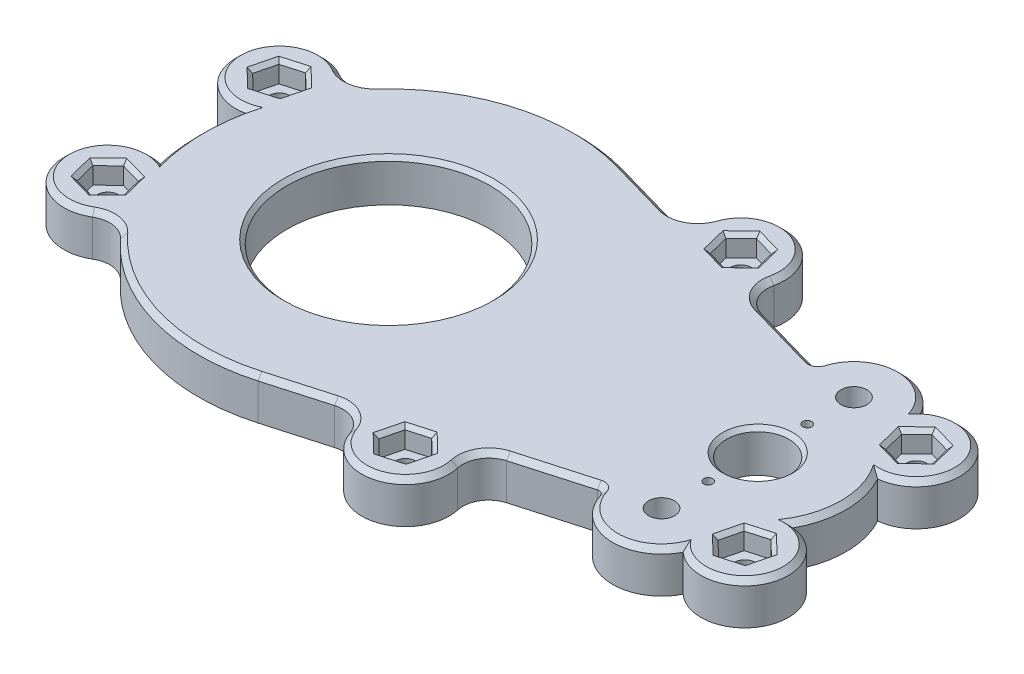
SolidWorks part; units mm, degrees
ref_plane "Front Plane" through (0, 0, 0) normal (0, 0, 1) x (1, 0, 0)
ref_plane "Top Plane" through (0, 0, 0) normal (0, 1, 0) x (1, 0, 0)
ref_plane "Right Plane" through (0, 0, 0) normal (1, 0, 0) x (0, 0, -1)
sketch "Sketch1" plane through (0, 0, 0) normal (0, 1, 0) x (1, 0, 0)
  line L0 (0, 73.0538) -> (0, -65.1274) construction
  line L1 (35.5, 6.365) -> (-28.5632, 24.502) construction
  line L2 (-70.6215, 0) -> (67.3742, 0) construction
  line L3 (35.5, -6.365) -> (-28.5632, -24.502) construction
  line L4 (4.5177, -15.1364) -> (0.1592, 0.2585)
  line L5 (0.1592, 0.2585) -> (4.6815, 1.5388)
  line L6 (4.6815, 1.5388) -> (9.04, -13.8561)
  line L7 (9.04, -13.8561) -> (9.5848, -15.7805)
  line L8 (9.5848, -15.7805) -> (5.0625, -17.0608)
  line L9 (5.0625, -17.0608) -> (4.5177, -15.1364)
  line L10 (-35.5, 0) -> (-60.5, 0) construction
  line L11 (-35.5, 0) -> (-35.5, 25) construction
  line L13 (-100, -75) -> (100, -75)
  line L14 (-100, -75) -> (-100, 75)
  line L15 (-100, 75) -> (100, 75)
  line L16 (100, -75) -> (100, 75)
  line L17 (-100, -75) -> (100, 75) construction
  line L18 (-100, 75) -> (100, -75) construction
  circle A0 centre (35.5, 0) radius 6
  circle A1 centre (-35.5, 0) radius 13.5
  circle A2 centre (-35.5, 0) radius 25.465 construction
  circle A3 centre (35.5, 0) radius 6.365 construction
  circle A4 centre (-60.5, 0) radius 2
  circle A5 centre (-35.5, 25) radius 2
  circle A6 centre (-10.5, 0) radius 2
  circle A7 centre (-35.5, -25) radius 2
  circle A8 centre (35.5, 18.5) radius 2.5
  circle A9 centre (35.5, -18.5) radius 2.5
  point P35 (0, 0)
  dimension "D1" = 12
  dimension "D2" = 27
  dimension "D5" = 50.93
  dimension "D6" = 12.73
  dimension "D12" = 4
  dimension "D19" = 5
  dimension "D3" = 71
  dimension "D4" = 35.5
  dimension "D7" = 90
  dimension "D8" = 27.5
  dimension "D9" = 4.7
  dimension "D10" = 16
  dimension "D11" = 2
  dimension "D13" = 25
  dimension "D15" = 90
  dimension "D16" = 25
  dimension "D17" = 200
  dimension "D18" = 150
  dimension "D20" = 18.5
  dimension "D14" = 4
extrude "Boss-Extrude1" add sketch "Sketch1" along normal blind 4
sketch "Sketch3" plane through (0, 4, 0) normal (0, 1, 0) x (1, 0, 0)
  line L0 (-26.5739, 31.2502) -> (39.0704, 12.5001)
  line L1 (-100, -75) -> (100, -75)
  line L2 (-100, -75) -> (-100, 75)
  line L3 (-100, 75) -> (100, 75)
  line L4 (100, -75) -> (100, 75)
  line L5 (-35.5, 0) -> (35.5, 0) construction
  line L6 (-26.5739, -31.2502) -> (39.0704, -12.5001)
  arc A0 (-26.5739, 31.2502) -> (-26.5739, -31.2502) centre (-35.5, 0) ccw
  arc A1 (39.0704, -12.5001) -> (39.0704, 12.5001) centre (35.5, 0) ccw
  dimension "D1" = 65
  dimension "D2" = 26
extrude "Boss-Extrude2" add sketch "Sketch3" along normal blind 8.25
sketch "Sketch6" plane through (0, 12.25, 0) normal (0, 1, 0) x (1, 0, 0)
  circle A0 centre (35.5, 18.5) radius 5.4
  circle A1 centre (35.5, -18.5) radius 5.4
  dimension "D1" = 10.8
extrude "Cut-Extrude2" cut sketch "Sketch6" against normal up to surface (8.25 mm away) up to face at (-35.5, 4, 27)
fillet "Fillet1" radius 2.5 4 edges at (9.5848, 2, 15.7805) (5.0625, 2, 17.0608) (4.6815, 2, -1.5388) (0.1592, 2, -0.2585)
fillet "Fillet2" radius 5 4 edges at (36.5847, 8.125, 13.2101) (31.7849, 8.125, 14.5811) (36.5847, 8.125, -13.2101) (31.7849, 8.125, -14.5811)
sketch "Sketch2" plane through (0, 4, 0) normal (0, 1, 0) x (1, 0, 0)
  line L0 (29.5, 0) -> (41.5, 0) construction
  line L1 (35.5, 0) -> (35.5, -6) construction
  line L2 (35.5, 0) -> (35.5, 6) construction
  circle A0 centre (-35.5, 25) radius 4.4
  circle A1 centre (-10.5, 0) radius 4.4
  circle A2 centre (-35.5, -25) radius 4.4
  circle A3 centre (-60.5, 0) radius 4.4
  circle A4 centre (35.5, 0) radius 6 construction
  circle A7 centre (35.5, 18.5) radius 5.4
  circle A8 centre (35.5, -18.5) radius 5.4
  arc A9 (40.6003, 16.7261) -> (30.3389, 20.0883) centre (35.5, 18.5) ccw construction
  dimension "D1" = 8.8
extrude "Cut-Extrude1" cut sketch "Sketch2" against normal blind 2
sketch "Sketch8" plane through (0, 0, 0) normal (0, -1, 0) x (1, 0, 0)
  line L0 (-35.5, 0) -> (-100, 0) construction
  line L1 (-100, -75) -> (-100, 75) construction
  line L2 (-35.5, 0) -> (100, 0) construction
  line L3 (100, 75) -> (100, -75) construction
  line L4 (49.5, 21.4955) -> (49.5, -20.5045) construction
  line L5 (0, 32.8542) -> (0, -34.16) construction
  line L6 (-73, 27.0496) -> (-73, -26.9504) construction
  line L11 (-26.5739, -31.2502) -> (24.1868, -16.7513)
  line L12 (24.1868, 16.7513) -> (-26.5739, 31.2502)
  line L13 (-26.5739, -31.2502) -> (24.1868, -16.7513) construction
  line L14 (24.1868, 16.7513) -> (-26.5739, 31.2502) construction
  circle A0 centre (-35.5, 0) radius 32.5 construction
  arc A1 (-26.5739, 31.2502) -> (-26.5739, -31.2502) centre (-35.5, 0) ccw construction
  circle A13 centre (49.5, 16.5) radius 2
  circle A14 centre (-73, 16.5) radius 2
  circle A15 centre (0, 32.25) radius 2
  circle A16 centre (49.5, 16.5) radius 4.4 construction
  circle A17 centre (0, 32.25) radius 4.4 construction
  circle A18 centre (-73, 16.5) radius 4.4 construction
  circle A19 centre (35.5, 18.5) radius 5.4 construction
  arc A20 (40.6003, 16.7261) -> (30.3389, 20.0883) centre (35.5, 18.5) ccw construction
  circle A21 centre (35.5, -18.5) radius 5.4 construction
  circle A22 centre (-73, -16.5) radius 4.4 construction
  circle A23 centre (-73, -16.5) radius 2
  circle A24 centre (0, -32.25) radius 4.4 construction
  circle A25 centre (0, -32.25) radius 2
  circle A26 centre (49.5, -16.5) radius 4.4 construction
  circle A27 centre (49.5, -16.5) radius 2
  circle A28 centre (49.5, 16.5) radius 8.4 construction
  circle A29 centre (0, 32.25) radius 8.4 construction
  circle A30 centre (-73, 16.5) radius 8.4 construction
  arc A44 (30.3389, -20.0883) -> (40.6003, -16.7261) centre (35.5, -18.5) ccw
  arc A45 (42.5943, -10.8936) -> (40.6003, -16.7261) centre (45.3228, -15.0835) ccw
  arc A46 (42.5943, -10.8936) -> (42.5943, 10.8936) centre (35.5, 0) ccw
  arc A47 (40.6003, 16.7261) -> (42.5943, 10.8936) centre (45.3228, 15.0835) ccw
  arc A48 (30.3389, -20.0883) -> (24.1868, -16.7513) centre (25.5601, -21.559) ccw
  arc A49 (40.6003, 16.7261) -> (30.3389, 20.0883) centre (35.5, 18.5) ccw
  arc A50 (24.1868, 16.7513) -> (30.3389, 20.0883) centre (25.5601, 21.559) ccw
  arc A51 (-26.5739, 31.2502) -> (-26.5739, -31.2502) centre (-35.5, 0) ccw
  arc A52 (30.3389, -20.0883) -> (40.6003, -16.7261) centre (35.5, -18.5) ccw construction
  arc A53 (42.5943, -10.8936) -> (40.6003, -16.7261) centre (45.3228, -15.0835) ccw construction
  arc A54 (42.5943, -10.8936) -> (42.5943, 10.8936) centre (35.5, 0) ccw construction
  arc A55 (40.6003, 16.7261) -> (42.5943, 10.8936) centre (45.3228, 15.0835) ccw construction
  arc A56 (30.3389, -20.0883) -> (24.1868, -16.7513) centre (25.5601, -21.559) ccw construction
  arc A57 (40.6003, 16.7261) -> (30.3389, 20.0883) centre (35.5, 18.5) ccw construction
  arc A58 (24.1868, 16.7513) -> (30.3389, 20.0883) centre (25.5601, 21.559) ccw construction
  arc A59 (-26.5739, 31.2502) -> (-26.5739, -31.2502) centre (-35.5, 0) ccw construction
  dimension "D1" = 0
  dimension "D2" = 4
  dimension "D4" = 33
  dimension "D5" = 49.5
  dimension "D3" = 8.8
  dimension "D8" = 16.8
  dimension "D6" = 64.5
  dimension "D7" = 73
extrude "Cut-Extrude3" cut sketch "Sketch8" against normal through all both and the other way through all
sketch "Sketch13" plane through (0, 12.25, 0) normal (0, 1, 0) x (1, 0, 0)
  line L0 (-100, 0) -> (100, 0) construction
  line L1 (-100, 75) -> (-100, -75) construction
  line L2 (100, -75) -> (100, 75) construction
  line L5 (-8.1313, 30.1424) -> (-25.4754, 35.0964)
  line L6 (5.7914, -26.1656) -> (25.2854, -20.5975)
  line L7 (-25.4754, -35.0964) -> (25.2854, -20.5975)
  line L8 (25.2854, 20.5975) -> (-25.4754, 35.0964)
  line L9 (-25.4754, -35.0964) -> (-8.1313, -30.1424)
  line L10 (25.2854, 20.5975) -> (5.7914, 26.1656)
  arc A0 (5.7914, 26.1656) -> (-8.1313, 30.1424) centre (0, 32.25) ccw
  arc A1 (50.4188, 8.1504) -> (43.8854, 22.7479) centre (49.5, 16.5) ccw
  arc A2 (-65.6518, 20.5699) -> (-71.0361, 8.3328) centre (-73, 16.5) ccw
  arc A3 (-65.6518, -20.5699) -> (-71.0361, -8.3328) centre (-73, -16.5) cw
  arc A4 (5.7914, -26.1656) -> (-8.1313, -30.1424) centre (0, -32.25) cw
  arc A5 (50.4188, -8.1504) -> (43.8854, -22.7479) centre (49.5, -16.5) cw
  arc A14 (-71.0361, 8.3328) -> (-71.0361, -8.3328) centre (-35.5, 0) ccw
  arc A15 (-65.6518, -20.5699) -> (-25.4754, -35.0964) centre (-35.5, 0) ccw
  arc A22 (44.3783, 15.412) -> (26.5158, 21.2649) centre (35.5, 18.5) ccw
  arc A23 (44.3783, 15.412) -> (44.7771, 14.2455) centre (45.3228, 15.0835) ccw
  arc A24 (44.7771, -14.2455) -> (44.7771, 14.2455) centre (35.5, 0) ccw
  arc A25 (44.7771, -14.2455) -> (44.3783, -15.412) centre (45.3228, -15.0835) ccw
  arc A26 (26.5158, -21.2649) -> (44.3783, -15.412) centre (35.5, -18.5) ccw
  arc A27 (26.5158, -21.2649) -> (25.2854, -20.5975) centre (25.5601, -21.559) ccw
  arc A28 (-25.4754, 35.0964) -> (-25.4754, -35.0964) centre (-35.5, 0) ccw
  arc A29 (25.2854, 20.5975) -> (26.5158, 21.2649) centre (25.5601, 21.559) ccw
  arc A30 (43.8854, 22.7479) -> (26.5158, 21.2649) centre (35.5, 18.5) ccw
  arc A32 (50.4188, -8.1504) -> (50.4188, 8.1504) centre (35.5, 0) ccw
  arc A34 (26.5158, -21.2649) -> (43.8854, -22.7479) centre (35.5, -18.5) ccw
  arc A35 (26.5158, -21.2649) -> (25.2854, -20.5975) centre (25.5601, -21.559) ccw
  arc A36 (-25.4754, 35.0964) -> (-65.6518, 20.5699) centre (-35.5, 0) ccw
  arc A37 (25.2854, 20.5975) -> (26.5158, 21.2649) centre (25.5601, 21.559) ccw
  dimension "D1" = 16.8
  dimension "D2" = 4
extrude "Cut-Extrude6" cut sketch "Sketch13" against normal through all both and the other way through all flip side to cut
fillet "Fillet4" radius 5 6 edges at (-65.6518, 6.125, 20.5699) (-65.6518, 6.125, -20.5699) (-8.1313, 6.125, -30.1424) (5.7914, 6.125, -26.1656) (5.7914, 6.125, 26.1656) (-8.1313, 6.125, 30.1424)
sketch "Sketch16" plane through (0, 12.25, 0) normal (0, 1, 0) x (1, 0, 0)
  line L12 (-25.4754, -35.0964) -> (-14.035, -31.8287)
  line L13 (11.6951, -24.4793) -> (25.2854, -20.5975)
  line L14 (25.2854, 20.5975) -> (11.6951, 24.4793)
  line L15 (-14.035, 31.8287) -> (-25.4754, 35.0964)
  line L16 (-25.4754, -35.0964) -> (-14.035, -31.8287)
  line L17 (11.6951, -24.4793) -> (25.2854, -20.5975)
  line L18 (25.2854, 20.5975) -> (11.6951, 24.4793)
  line L19 (-14.035, 31.8287) -> (-25.4754, 35.0964)
  arc A60 (-71.0361, 8.3328) -> (-71.0361, -8.3328) centre (-35.5, 0) ccw
  arc A61 (-71.0361, -8.3328) -> (-68.692, -23.7112) centre (-73, -16.5) ccw
  arc A62 (-62.4376, -24.6296) -> (-68.692, -23.7112) centre (-66.1277, -28.0035) ccw
  arc A63 (-62.4376, -24.6296) -> (-25.4754, -35.0964) centre (-35.5, 0) ccw
  arc A64 (-7.9372, -34.9997) -> (-14.035, -31.8287) centre (-12.6617, -36.6364) ccw
  arc A65 (-7.9372, -34.9997) -> (8.1921, -30.3926) centre (0, -32.25) ccw
  arc A66 (11.6951, -24.4793) -> (8.1921, -30.3926) centre (13.0683, -29.2871) ccw
  arc A67 (26.5158, -21.2649) -> (25.2854, -20.5975) centre (25.5601, -21.559) ccw
  arc A68 (26.5158, -21.2649) -> (43.8854, -22.7479) centre (35.5, -18.5) ccw
  arc A69 (43.8854, -22.7479) -> (50.4188, -8.1504) centre (49.5, -16.5) ccw
  arc A70 (50.4188, -8.1504) -> (50.4188, 8.1504) centre (35.5, 0) ccw
  arc A71 (50.4188, 8.1504) -> (43.8854, 22.7479) centre (49.5, 16.5) ccw
  arc A72 (43.8854, 22.7479) -> (26.5158, 21.2649) centre (35.5, 18.5) ccw
  arc A73 (25.2854, 20.5975) -> (26.5158, 21.2649) centre (25.5601, 21.559) ccw
  arc A74 (8.1921, 30.3926) -> (11.6951, 24.4793) centre (13.0683, 29.2871) ccw
  arc A75 (8.1921, 30.3926) -> (-7.9372, 34.9997) centre (0, 32.25) ccw
  arc A76 (-14.035, 31.8287) -> (-7.9372, 34.9997) centre (-12.6617, 36.6364) ccw
  arc A77 (-25.4754, 35.0964) -> (-62.4376, 24.6296) centre (-35.5, 0) ccw
  arc A78 (-68.692, 23.7112) -> (-62.4376, 24.6296) centre (-66.1277, 28.0035) ccw
  arc A79 (-68.692, 23.7112) -> (-71.0361, 8.3328) centre (-73, 16.5) ccw
  arc A80 (-71.0361, 8.3328) -> (-71.0361, -8.3328) centre (-35.5, 0) ccw
  arc A81 (-71.0361, -8.3328) -> (-68.692, -23.7112) centre (-73, -16.5) ccw
  arc A82 (-62.4376, -24.6296) -> (-68.692, -23.7112) centre (-66.1277, -28.0035) ccw
  arc A83 (-62.4376, -24.6296) -> (-25.4754, -35.0964) centre (-35.5, 0) ccw
  arc A84 (-7.9372, -34.9997) -> (-14.035, -31.8287) centre (-12.6617, -36.6364) ccw
  arc A85 (-7.9372, -34.9997) -> (8.1921, -30.3926) centre (0, -32.25) ccw
  arc A86 (11.6951, -24.4793) -> (8.1921, -30.3926) centre (13.0683, -29.2871) ccw
  arc A87 (26.5158, -21.2649) -> (25.2854, -20.5975) centre (25.5601, -21.559) ccw
  arc A88 (26.5158, -21.2649) -> (43.8854, -22.7479) centre (35.5, -18.5) ccw
  arc A89 (43.8854, -22.7479) -> (50.4188, -8.1504) centre (49.5, -16.5) ccw
  arc A90 (50.4188, -8.1504) -> (50.4188, 8.1504) centre (35.5, 0) ccw
  arc A91 (50.4188, 8.1504) -> (43.8854, 22.7479) centre (49.5, 16.5) ccw
  arc A92 (43.8854, 22.7479) -> (26.5158, 21.2649) centre (35.5, 18.5) ccw
  arc A93 (25.2854, 20.5975) -> (26.5158, 21.2649) centre (25.5601, 21.559) ccw
  arc A94 (8.1921, 30.3926) -> (11.6951, 24.4793) centre (13.0683, 29.2871) ccw
  arc A95 (8.1921, 30.3926) -> (-7.9372, 34.9997) centre (0, 32.25) ccw
  arc A96 (-14.035, 31.8287) -> (-7.9372, 34.9997) centre (-12.6617, 36.6364) ccw
  arc A97 (-25.4754, 35.0964) -> (-62.4376, 24.6296) centre (-35.5, 0) ccw
  arc A98 (-68.692, 23.7112) -> (-62.4376, 24.6296) centre (-66.1277, 28.0035) ccw
  arc A99 (-68.692, 23.7112) -> (-71.0361, 8.3328) centre (-73, 16.5) ccw
  dimension "D1" = 0
extrude "Cut-Extrude7" cut sketch "Sketch16" against normal up to surface (10.25 mm away) up to face at (-35.5, 2, -23)
sketch "Sketch17" plane through (0, 0, 0) normal (0, -1, 0) x (1, 0, 0)
  line L4 (4.3815, 14.6553) -> (0.8403, 2.1469)
  line L5 (5.3625, 0.8666) -> (8.9038, 13.375)
  line L6 (4.3815, 14.6553) -> (0.8403, 2.1469)
  line L7 (5.3625, 0.8666) -> (8.9038, 13.375)
  circle A6 centre (-10.5, 0) radius 2
  circle A7 centre (-10.5, 0) radius 2
  arc A8 (2.4216, -0.8943) -> (5.3625, 0.8666) centre (2.9571, 1.5477) ccw
  arc A9 (0.8403, 2.1469) -> (2.4216, -0.8943) centre (3.2457, 1.4659) ccw
  arc A10 (8.9038, 13.375) -> (7.3224, 16.4163) centre (6.4983, 14.056) ccw
  arc A11 (7.3224, 16.4163) -> (4.3815, 14.6553) centre (6.787, 13.9743) ccw
  arc A12 (2.4216, -0.8943) -> (5.3625, 0.8666) centre (2.9571, 1.5477) ccw
  arc A13 (0.8403, 2.1469) -> (2.4216, -0.8943) centre (3.2457, 1.4659) ccw
  arc A14 (8.9038, 13.375) -> (7.3224, 16.4163) centre (6.4983, 14.056) ccw
  arc A15 (7.3224, 16.4163) -> (4.3815, 14.6553) centre (6.787, 13.9743) ccw
  circle A17 centre (-35.5, -25) radius 2
  circle A18 centre (-35.5, -25) radius 2
  circle A20 centre (-35.5, 25) radius 2
  circle A21 centre (-35.5, 25) radius 2
  circle A23 centre (-60.5, 0) radius 2
  circle A24 centre (-60.5, 0) radius 2
  dimension "D1" = 0
  dimension "D2" = 0
  dimension "D3" = 0
  dimension "D4" = 0
  dimension "D5" = 0
extrude "Boss-Extrude3" add sketch "Sketch17" against normal up to surface (2 mm away) up to face at (35.5, 2, -16)
sketch "Sketch18" plane through (0, 2, 0) normal (0, 1, 0) x (1, 0, 0)
  line L8 (-25.4754, -35.0964) -> (-14.035, -31.8287)
  line L9 (11.6951, -24.4793) -> (25.2854, -20.5975)
  line L10 (25.2854, 20.5975) -> (11.6951, 24.4793)
  line L11 (-14.035, 31.8287) -> (-25.4754, 35.0964)
  line L12 (-25.4754, -35.0964) -> (-14.035, -31.8287)
  line L13 (11.6951, -24.4793) -> (25.2854, -20.5975)
  line L14 (25.2854, 20.5975) -> (11.6951, 24.4793)
  line L15 (-14.035, 31.8287) -> (-25.4754, 35.0964)
  circle A20 centre (-35.5, 0) radius 13.5
  circle A21 centre (0, 32.25) radius 2
  circle A22 centre (-73, 16.5) radius 2
  circle A23 centre (-73, -16.5) radius 2
  circle A24 centre (0, 32.25) radius 2 construction
  circle A25 centre (-35.5, 0) radius 13.5 construction
  circle A26 centre (0, -32.25) radius 2
  circle A27 centre (35.5, -18.5) radius 2.5
  circle A28 centre (35.5, 0) radius 6
  circle A29 centre (49.5, -16.5) radius 2
  circle A30 centre (35.5, 18.5) radius 2.5
  circle A31 centre (49.5, 16.5) radius 2
  circle A32 centre (-73, 16.5) radius 2 construction
  circle A33 centre (-73, -16.5) radius 2 construction
  circle A34 centre (0, -32.25) radius 2 construction
  circle A35 centre (35.5, -18.5) radius 2.5 construction
  circle A36 centre (35.5, 0) radius 6 construction
  circle A37 centre (35.5, 18.5) radius 2.5 construction
  circle A38 centre (49.5, 16.5) radius 2 construction
  circle A39 centre (49.5, -16.5) radius 2 construction
  arc A40 (-68.692, 23.7112) -> (-71.0361, 8.3328) centre (-73, 16.5) ccw
  arc A41 (-71.0361, 8.3328) -> (-71.0361, -8.3328) centre (-35.5, 0) ccw
  arc A42 (-71.0361, -8.3328) -> (-68.692, -23.7112) centre (-73, -16.5) ccw
  arc A43 (-62.4376, -24.6296) -> (-68.692, -23.7112) centre (-66.1277, -28.0035) ccw
  arc A44 (-62.4376, -24.6296) -> (-25.4754, -35.0964) centre (-35.5, 0) ccw
  arc A45 (-7.9372, -34.9997) -> (-14.035, -31.8287) centre (-12.6617, -36.6364) ccw
  arc A46 (-7.9372, -34.9997) -> (8.1921, -30.3926) centre (0, -32.25) ccw
  arc A47 (11.6951, -24.4793) -> (8.1921, -30.3926) centre (13.0683, -29.2871) ccw
  arc A48 (26.5158, -21.2649) -> (25.2854, -20.5975) centre (25.5601, -21.559) ccw
  arc A49 (26.5158, -21.2649) -> (43.8854, -22.7479) centre (35.5, -18.5) ccw
  arc A50 (43.8854, -22.7479) -> (50.4188, -8.1504) centre (49.5, -16.5) ccw
  arc A51 (50.4188, -8.1504) -> (50.4188, 8.1504) centre (35.5, 0) ccw
  arc A52 (50.4188, 8.1504) -> (43.8854, 22.7479) centre (49.5, 16.5) ccw
  arc A53 (43.8854, 22.7479) -> (26.5158, 21.2649) centre (35.5, 18.5) ccw
  arc A54 (25.2854, 20.5975) -> (26.5158, 21.2649) centre (25.5601, 21.559) ccw
  arc A55 (8.1921, 30.3926) -> (11.6951, 24.4793) centre (13.0683, 29.2871) ccw
  arc A56 (8.1921, 30.3926) -> (-7.9372, 34.9997) centre (0, 32.25) ccw
  arc A57 (-14.035, 31.8287) -> (-7.9372, 34.9997) centre (-12.6617, 36.6364) ccw
  arc A58 (-25.4754, 35.0964) -> (-62.4376, 24.6296) centre (-35.5, 0) ccw
  arc A59 (-68.692, 23.7112) -> (-62.4376, 24.6296) centre (-66.1277, 28.0035) ccw
  arc A60 (-68.692, 23.7112) -> (-71.0361, 8.3328) centre (-73, 16.5) ccw
  arc A61 (-71.0361, 8.3328) -> (-71.0361, -8.3328) centre (-35.5, 0) ccw
  arc A62 (-71.0361, -8.3328) -> (-68.692, -23.7112) centre (-73, -16.5) ccw
  arc A63 (-62.4376, -24.6296) -> (-68.692, -23.7112) centre (-66.1277, -28.0035) ccw
  arc A64 (-62.4376, -24.6296) -> (-25.4754, -35.0964) centre (-35.5, 0) ccw
  arc A65 (-7.9372, -34.9997) -> (-14.035, -31.8287) centre (-12.6617, -36.6364) ccw
  arc A66 (-7.9372, -34.9997) -> (8.1921, -30.3926) centre (0, -32.25) ccw
  arc A67 (11.6951, -24.4793) -> (8.1921, -30.3926) centre (13.0683, -29.2871) ccw
  arc A68 (26.5158, -21.2649) -> (25.2854, -20.5975) centre (25.5601, -21.559) ccw
  arc A69 (26.5158, -21.2649) -> (43.8854, -22.7479) centre (35.5, -18.5) ccw
  arc A70 (43.8854, -22.7479) -> (50.4188, -8.1504) centre (49.5, -16.5) ccw
  arc A71 (50.4188, -8.1504) -> (50.4188, 8.1504) centre (35.5, 0) ccw
  arc A72 (50.4188, 8.1504) -> (43.8854, 22.7479) centre (49.5, 16.5) ccw
  arc A73 (43.8854, 22.7479) -> (26.5158, 21.2649) centre (35.5, 18.5) ccw
  arc A74 (25.2854, 20.5975) -> (26.5158, 21.2649) centre (25.5601, 21.559) ccw
  arc A75 (8.1921, 30.3926) -> (11.6951, 24.4793) centre (13.0683, 29.2871) ccw
  arc A76 (8.1921, 30.3926) -> (-7.9372, 34.9997) centre (0, 32.25) ccw
  arc A77 (-14.035, 31.8287) -> (-7.9372, 34.9997) centre (-12.6617, 36.6364) ccw
  arc A78 (-25.4754, 35.0964) -> (-62.4376, 24.6296) centre (-35.5, 0) ccw
  arc A79 (-68.692, 23.7112) -> (-62.4376, 24.6296) centre (-66.1277, 28.0035) ccw
  dimension "D1" = 0
extrude "Boss-Extrude4" add sketch "Sketch18" along normal blind 6
sketch "Sketch19" plane through (0, 0, 0) normal (0, -1, 0) x (1, 0, 0)
  line L0 (25.975, 0) -> (45.025, 0) construction
  circle A0 centre (-35.5, 0) radius 19.5
  circle A1 centre (35.5, 0) radius 9.525 construction
  circle A2 centre (35.5, 9.525) radius 0.875
  circle A3 centre (35.5, -9.525) radius 0.875
  dimension "D1" = 39
  dimension "D2" = 19.05
  dimension "D3" = 1.75
extrude "Cut-Extrude8" cut sketch "Sketch19" against normal through all both and the other way through all
sketch "Sketch20" plane through (0, 0, 0) normal (0, -1, 0) x (1, 0, 0)
  line L1 (40.292, 18.5) -> (37.896, 22.65)
  line L2 (37.896, 22.65) -> (33.104, 22.65)
  line L3 (33.104, 22.65) -> (30.708, 18.5)
  line L4 (30.708, 18.5) -> (33.104, 14.35)
  line L5 (33.104, 14.35) -> (37.896, 14.35)
  line L6 (37.896, 14.35) -> (40.292, 18.5)
  line L7 (40.292, -18.5) -> (37.896, -14.35)
  line L8 (37.896, -14.35) -> (33.104, -14.35)
  line L9 (33.104, -14.35) -> (30.708, -18.5)
  line L10 (30.708, -18.5) -> (33.104, -22.65)
  line L11 (33.104, -22.65) -> (37.896, -22.65)
  line L12 (37.896, -22.65) -> (40.292, -18.5)
  circle A0 centre (35.5, 18.5) radius 4.15 construction
  circle A1 centre (35.5, -18.5) radius 4.15 construction
  dimension "D1" = 8.3
  dimension "D2" = 8.3
extrude "Cut-Extrude9" cut sketch "Sketch20" against normal blind 4
sketch "Sketch21" plane through (0, 8, 0) normal (0, 1, 0) x (1, 0, 0)
  line L0 (25.2854, 20.5975) -> (11.6951, 24.4793) construction
  line L1 (-70.0127, 13.6093) -> (-69.0029, 17.6417)
  line L2 (-69.0029, 17.6417) -> (-71.9902, 20.5324)
  line L3 (-71.9902, 20.5324) -> (-75.9873, 19.3907)
  line L4 (-75.9873, 19.3907) -> (-76.9971, 15.3583)
  line L5 (-76.9971, 15.3583) -> (-74.0098, 12.4676)
  line L6 (-74.0098, 12.4676) -> (-70.0127, 13.6093)
  line L7 (-70.0127, -13.6093) -> (-74.0098, -12.4676)
  line L8 (-74.0098, -12.4676) -> (-76.9971, -15.3583)
  line L9 (-76.9971, -15.3583) -> (-75.9873, -19.3907)
  line L10 (-75.9873, -19.3907) -> (-71.9902, -20.5324)
  line L11 (-71.9902, -20.5324) -> (-69.0029, -17.6417)
  line L12 (-69.0029, -17.6417) -> (-70.0127, -13.6093)
  line L13 (3.9971, 31.1083) -> (2.9873, 35.1407)
  line L14 (2.9873, 35.1407) -> (-1.0098, 36.2824)
  line L15 (-1.0098, 36.2824) -> (-3.9971, 33.3917)
  line L16 (-3.9971, 33.3917) -> (-2.9873, 29.3593)
  line L17 (-2.9873, 29.3593) -> (1.0098, 28.2176)
  line L18 (1.0098, 28.2176) -> (3.9971, 31.1083)
  line L19 (50.5098, 12.4676) -> (53.4971, 15.3583)
  line L20 (53.4971, 15.3583) -> (52.4873, 19.3907)
  line L21 (52.4873, 19.3907) -> (48.4902, 20.5324)
  line L22 (48.4902, 20.5324) -> (45.5029, 17.6417)
  line L23 (45.5029, 17.6417) -> (46.5127, 13.6093)
  line L24 (46.5127, 13.6093) -> (50.5098, 12.4676)
  line L25 (53.4971, -15.3583) -> (50.5098, -12.4676)
  line L26 (50.5098, -12.4676) -> (46.5127, -13.6093)
  line L27 (46.5127, -13.6093) -> (45.5029, -17.6417)
  line L28 (45.5029, -17.6417) -> (48.4902, -20.5324)
  line L29 (48.4902, -20.5324) -> (52.4873, -19.3907)
  line L30 (52.4873, -19.3907) -> (53.4971, -15.3583)
  line L31 (3.9971, -31.1083) -> (1.0098, -28.2176)
  line L32 (1.0098, -28.2176) -> (-2.9873, -29.3593)
  line L33 (-2.9873, -29.3593) -> (-3.9971, -33.3917)
  line L34 (-3.9971, -33.3917) -> (-1.0098, -36.2824)
  line L35 (-1.0098, -36.2824) -> (2.9873, -35.1407)
  line L36 (2.9873, -35.1407) -> (3.9971, -31.1083)
  line L37 (11.6951, -24.4793) -> (25.2854, -20.5975) construction
  line L38 (-25.4754, -35.0964) -> (-14.035, -31.8287) construction
  line L39 (-14.035, 31.8287) -> (-25.4754, 35.0964) construction
  circle A0 centre (-73, 16.5) radius 3.6 construction
  circle A1 centre (-73, -16.5) radius 3.6 construction
  circle A2 centre (0, 32.25) radius 3.6 construction
  circle A3 centre (49.5, 16.5) radius 3.6 construction
  circle A4 centre (49.5, -16.5) radius 3.6 construction
  circle A5 centre (0, -32.25) radius 3.6 construction
  point P46 (-70.4966, -19.087)
  dimension "D1" = 7.2
  dimension "D2" = 7.2
  dimension "D3" = 7.2
  dimension "D4" = 7.2
  dimension "D5" = 7.2
  dimension "D6" = 7.2
extrude "Cut-Extrude10" cut sketch "Sketch21" against normal blind 4
chamfer "Chamfer1" distance 1 angle 45 24 edges at (-45.4449, 8, -35.1191) (-19.7552, 8, -33.4625) (-10.3549, 8, -32.2003) (2.307, 8, -40.327) (8.7665, 8, -26.7387) (18.4902, 8, -22.5384) (26.0369, 8, -20.68) (34.7003, 8, -27.8659) (57.1671, 8, -19.9316) (52.5, 8, 0) (57.1671, 8, 19.9316) (34.7003, 8, 27.8659) (26.0369, 8, 20.68) (18.4902, 8, 22.5384) (8.7665, 8, 26.7387) (2.307, 8, 40.327) (-10.3549, 8, 32.2003) (-19.7552, 8, 33.4625) (-45.4449, 8, 35.1191) (-65.4012, 8, 23.0566) (-81.3041, 8, 17.7658) (-72, 8, 0) (-81.3041, 8, -17.7658) (-65.4012, 8, -23.0566)
chamfer "Chamfer2" distance 0.75 angle 45 38 edges at (35.5, 8, 6) (-35.5, 8, -19.5) (46.9966, 8, -19.087) (50.4887, 8, -19.9616) (52.9922, 8, -17.3745) (52.0034, 8, -13.913) (46.0078, 8, -15.6255) (48.5113, 8, -13.0384) (3.4922, 8, -33.1245) (0.9887, 8, -35.7116) (-2.5034, 8, -34.837) (-3.4922, 8, -31.3755) (2.5034, 8, -29.663) (-0.9887, 8, -28.7884) (-69.5078, 8, -15.6255) (-70.4966, 8, -19.087) (-73.9887, 8, -19.9616) (-76.4922, 8, -17.3745) (-75.5034, 8, -13.913) (-72.0113, 8, -13.0384) (-69.5078, 8, 15.6255) (-72.0113, 8, 13.0384) (-75.5034, 8, 13.913) (-76.4922, 8, 17.3745) (-73.9887, 8, 19.9616) (-70.4966, 8, 19.087) (2.5034, 8, 29.663) (3.4922, 8, 33.1245) (0.9887, 8, 35.7116) (-2.5034, 8, 34.837) (-3.4922, 8, 31.3755) (-0.9887, 8, 28.7884) (52.0034, 8, 13.913) (48.5113, 8, 13.0384) (46.0078, 8, 15.6255) (46.9966, 8, 19.087) (52.9922, 8, 17.3745) (50.4887, 8, 19.9616)
